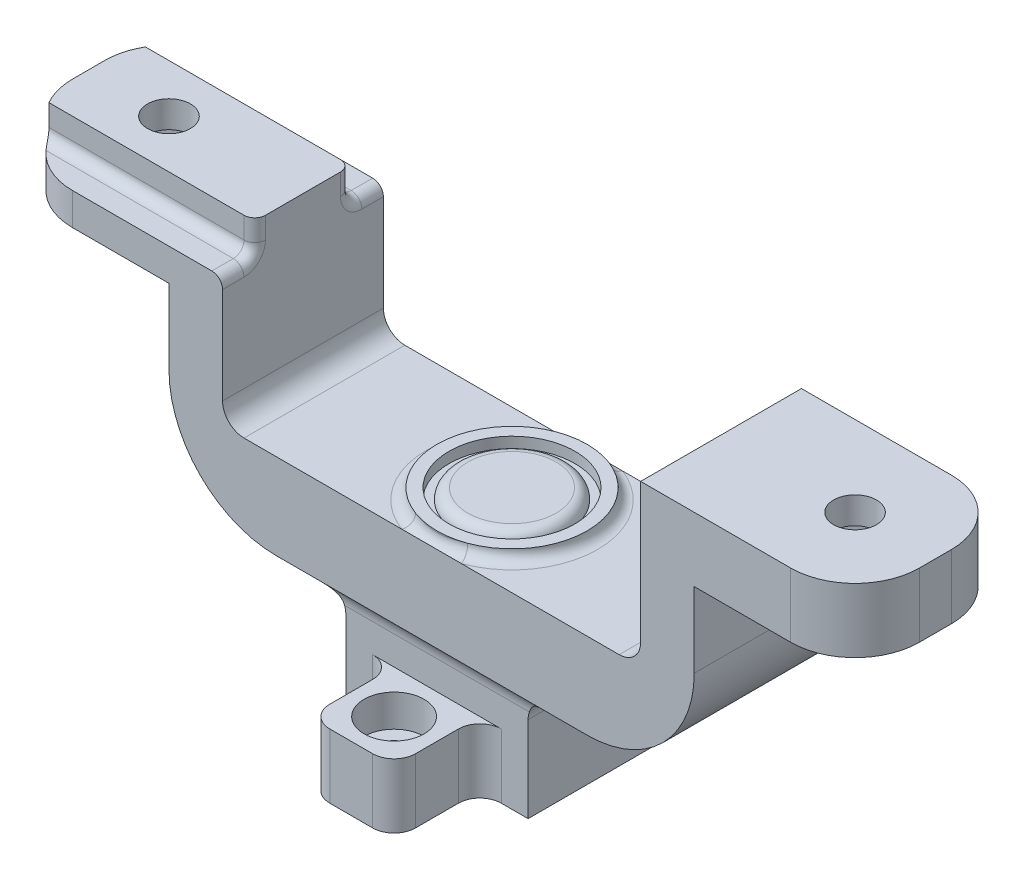
SolidWorks part; units mm, degrees
ref_plane "Спереди" through (0, 0, 0) normal (0, 0, 1) x (1, 0, 0)
ref_plane "Сверху" through (0, 0, 0) normal (0, 1, 0) x (1, 0, 0)
ref_plane "Справа" through (0, 0, 0) normal (1, 0, 0) x (0, 0, -1)
sketch "Sketch1" plane through (0, 0, 0) normal (0, 1, 0) x (1, 0, 0)
  line L1 (0, 0) -> (39, 0)
  line L2 (0, 0) -> (0, -15)
  line L3 (0, -15) -> (39, -15)
  line L4 (39, 0) -> (39, -15)
  dimension "D1" = 15
  dimension "D2" = 39
extrude "Boss-Extrude1" add sketch "Sketch1" along normal blind 8 contours L2 L3 L4 L1
sketch "Sketch2" plane through (0, 8, 0) normal (0, 1, 0) x (1, 0, 0)
  line L0 (19.5, 0) -> (19.5, -15) construction
  line L1 (0, 0) -> (39, 0) construction
  line L2 (0, -15) -> (39, -15) construction
  circle A0 centre (19.5, -7.5) radius 5.875
  circle A1 centre (19.5, -7.5) radius 5.125
  circle A2 centre (19.5, -7.5) radius 7
  dimension "D1" = 11.75
  dimension "D2" = 10.25
  dimension "D3" = 14
extrude "Boss-Extrude2" add sketch "Sketch2" along normal blind 1 contours L0 A2 A0 | A2 L0 A0 | L0 A1 | A1 L0 region at (24.3391, 8, 2.6609) region at (19.3435, 8, 1.0625) region at (21.6751, 8, 7.5) region at (17.3249, 8, 7.5)
fillet "Fillet1" radius 1 1 edges at (19.5, 9, 12.625)
fillet "Fillet2" radius 1 1 edges at (19.5, 8, 0.5)
sketch "Sketch3" plane through (0, 0, 0) normal (0, -1, 0) x (1, 0, 0)
  line L1 (0, 15) -> (-5, 15)
  line L2 (0, 15) -> (0, 0)
  line L3 (0, 0) -> (-5, 0)
  line L4 (-5, 15) -> (-5, 0)
  line L5 (39, 15) -> (44, 15)
  line L6 (39, 15) -> (39, 0)
  line L7 (39, 0) -> (44, 0)
  line L8 (44, 15) -> (44, 0)
  dimension "D1" = 5
  dimension "D2" = 5
  dimension "D3" = 15
  dimension "D4" = 15
extrude "Boss-Extrude3" add sketch "Sketch3" against normal blind 23
fillet "Fillet3" radius 2 2 edges
fillet "Fillet4" radius 10 2 edges at (44, 0, 7.5) (-5, 0, 7.5)
sketch "Sketch4" plane through (0, 23, 0) normal (0, 1, 0) x (1, 0, 0)
  line L0 (19.5, 0) -> (19.5, -15) construction
  line L1 (16.7161, 0) -> (22.2839, 0) construction
  line L2 (16.7161, -15) -> (22.2839, -15) construction
  line L3 (-5, -7.5) -> (44, -7.5) construction
  line L4 (-5, -15) -> (-5, 0) construction
  line L5 (44, 0) -> (44, -15) construction
  line L6 (-20, 0) -> (-5, -15) construction
  line L7 (-5, 0) -> (-20, 0)
  line L8 (-5, 0) -> (-5, -15)
  line L9 (-5, -15) -> (-20, -15)
  line L10 (-20, 0) -> (-20, -15)
  line L11 (44, 0) -> (59, 0)
  line L12 (44, 0) -> (44, -15)
  line L13 (44, -15) -> (59, -15)
  line L14 (59, 0) -> (59, -15)
  line L15 (44, -15) -> (59, 0) construction
  circle A0 centre (51.5, -7.5) radius 2
  circle A1 centre (-12.5, -7.5) radius 2
  dimension "D5" = 4
  dimension "D6" = 4
  dimension "D1" = 15
  dimension "D2" = 15
  dimension "D3" = 15
  dimension "D4" = 15
extrude "Boss-Extrude4" add sketch "Sketch4" against normal blind 6
sketch "Sketch5" plane through (0, 17, 0) normal (0, -1, 0) x (1, 0, 0)
  line L0 (-20, 0) -> (-20, 15) construction
  line L1 (-9, 5.4793) -> (-9, 9.5207)
  line L2 (-9, 9.5207) -> (-12.5, 11.5415)
  line L3 (-12.5, 11.5415) -> (-16, 9.5207)
  line L4 (-16, 9.5207) -> (-16, 5.4793)
  line L5 (-16, 5.4793) -> (-12.5, 3.4585)
  line L6 (-12.5, 3.4585) -> (-9, 5.4793)
  line L7 (55, 5.4793) -> (55, 9.5207)
  line L8 (55, 9.5207) -> (51.5, 11.5415)
  line L9 (51.5, 11.5415) -> (48, 9.5207)
  line L10 (48, 9.5207) -> (48, 5.4793)
  line L11 (48, 5.4793) -> (51.5, 3.4585)
  line L12 (51.5, 3.4585) -> (55, 5.4793)
  circle A0 centre (-12.5, 7.5) radius 3.5 construction
  circle A1 centre (51.5, 7.5) radius 3.5 construction
  dimension "D1" = 7
  dimension "D2" = 7
extrude "Cut-Extrude1" cut sketch "Sketch5" against normal blind 3.5
sketch "Sketch6" plane through (0, 23, 0) normal (0, 1, 0) x (1, 0, 0)
  line L0 (-20, -7.5) -> (19.5, -7.5) construction
  line L1 (-20, 0) -> (-20, -15) construction
  line L2 (19.5, 0) -> (19.5, -15) construction
  line L3 (16.7161, 0) -> (22.2839, 0) construction
  line L4 (16.7161, -15) -> (22.2839, -15) construction
  line L6 (-20, -12) -> (19.5, -12)
  line L7 (-20, -12) -> (-20, -15)
  line L8 (-20, -15) -> (19.5, -15)
  line L9 (19.5, -12) -> (19.5, -15)
  line L10 (19.5, -3) -> (-20, -3)
  line L11 (19.5, -3) -> (19.5, 0)
  line L12 (19.5, 0) -> (-20, 0)
  line L13 (-20, -3) -> (-20, 0)
  dimension "D1" = 3
  dimension "D2" = 3
extrude "Cut-Extrude2" cut sketch "Sketch6" against normal blind 3
fillet "Fillet5" radius 1 6 edges at (0, 20, 1.5) (0, 20, 13.5) (0, 21.5, 3) (0, 21.5, 12) (-10, 20, 12) (-10, 20, 3)
fillet "Fillet6" radius 6 4 edges at (59, 20, 0) (59, 20, 15) (-20, 18.5, 15) (-20, 18.5, 0)
sketch "Sketch7" plane through (0, 0, 0) normal (0, -1, 0) x (1, 0, 0)
  line L0 (19.5, 15) -> (19.5, 0) construction
  line L1 (5, 15) -> (34, 15) construction
  line L2 (5, 0) -> (34, 0) construction
  line L3 (5, 7.5) -> (34, 7.5) construction
  line L4 (5, 15) -> (5, 0) construction
  line L5 (34, 0) -> (34, 15) construction
  line L7 (11, 14.5) -> (28, 14.5)
  line L8 (11, 14.5) -> (11, 0.5)
  line L9 (11, 0.5) -> (28, 0.5)
  line L10 (28, 14.5) -> (28, 0.5)
  dimension "D1" = 17
  dimension "D2" = 14
  dimension "D3" = 7
  dimension "D4" = 8.5
extrude "Boss-Extrude5" add sketch "Sketch7" along normal blind 10
sketch "Sketch8" plane through (0, -10, 0) normal (0, -1, 0) x (1, 0, 0)
  line L1 (19.5, 15) -> (19.5, 0) construction
  line L2 (5, 15) -> (34, 15) construction
  line L3 (5, 0) -> (34, 0) construction
  line L4 (28, 14.5) -> (11, 14.5) construction
  line L6 (15.5, 14.5) -> (23.5, 14.5)
  line L7 (15.5, 14.5) -> (15.5, 22.5)
  line L8 (15.5, 22.5) -> (23.5, 22.5)
  line L9 (23.5, 14.5) -> (23.5, 22.5)
  line L10 (5, 7.5) -> (34, 7.5) construction
  line L11 (5, 15) -> (5, 0) construction
  line L12 (34, 0) -> (34, 15) construction
  line L13 (11, 0.5) -> (28, 0.5) construction
  line L14 (15.5, 0.5) -> (23.5, 0.5)
  line L15 (15.5, 0.5) -> (15.5, -7.5)
  line L17 (15.5, -7.5) -> (23.5, -7.5)
  line L18 (23.5, 0.5) -> (23.5, -7.5)
  line L19 (15.5, 22.5) -> (23.5, 14.5) construction
  circle A0 centre (19.5, 18.5) radius 1.5
  circle A1 centre (19.5, -3.5) radius 1.5
  dimension "D4" = 8
  dimension "D7" = 3
  dimension "D1" = 8
  dimension "D2" = 8
  dimension "D3" = 4
  dimension "D5" = 8
  dimension "D6" = 4
extrude "Boss-Extrude6" add sketch "Sketch8" against normal blind 6
sketch "Sketch9" plane through (0, -4, 0) normal (0, 1, 0) x (1, 0, 0)
  circle A0 centre (19.5, 3.5) radius 2.8
  circle A1 centre (19.5, -18.5) radius 2.8
  dimension "D1" = 5.6
  dimension "D2" = 5.6
extrude "Cut-Extrude3" cut sketch "Sketch9" against normal blind 3
fillet "Fillet7" radius 2 4 edges at (11, 0, 7.5) (19.5, 0, 0.5) (28, 0, 7.5) (19.5, 0, 14.5)
fillet "Fillet8" radius 2 8 edges at (15.5, -7, 0.5) (15.5, -7, -7.5) (23.5, -7, -7.5) (23.5, -7, 0.5) (15.5, -7, 22.5) (23.5, -7, 22.5) (15.5, -7, 14.5) (23.5, -7, 14.5)
